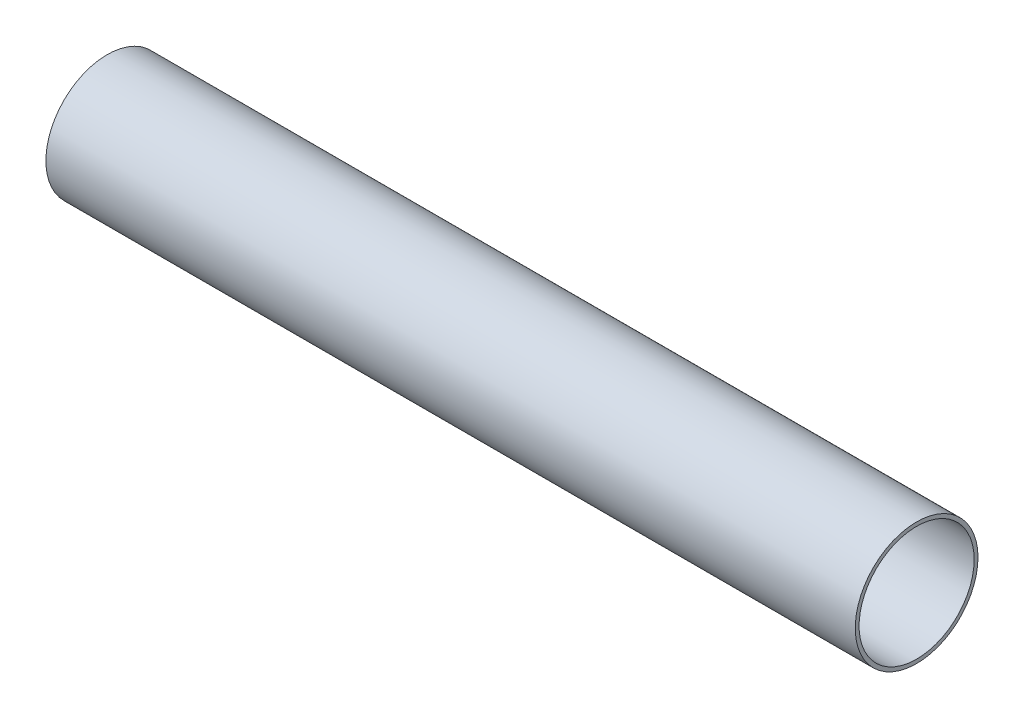
SolidWorks part; units mm, degrees
other "Exploded View1" [suppressed]
material "PC High Viscosity"
ref_plane "Front Plane" through (0, 0, 0) normal (0, 0, 1) x (1, 0, 0)
ref_plane "Top Plane" through (0, 0, 0) normal (0, 1, 0) x (1, 0, 0)
ref_plane "Right Plane" through (0, 0, 0) normal (1, 0, 0) x (0, 0, -1)
sketch "Sketch1" plane through (0, 0, 0) normal (1, 0, 0) x (0, 0, -1)
  circle A0 centre (0, 0) radius 25.4
  dimension "D1" = 50.8
extrude "Extrude-Thin1" add sketch "Sketch1" along normal mid plane 334.9625 thin thin type one direction reverse wall 1.5875
sketch "Sketch2" plane through (0, 0, 0) normal (0, 0, 1) x (1, 0, 0)
  line L0 (-167.4812, -25.4) -> (167.4812, -25.4) construction
  line L1 (112.2073, -25.4) -> (133.2072, -25.4)
  line L2 (112.2073, -25.4) -> (112.2073, 25.4)
  line L3 (112.2073, 25.4) -> (133.2072, 25.4)
  line L4 (133.2072, -25.4) -> (133.2072, 25.4)
  line L5 (167.4812, 25.4) -> (-167.4812, 25.4) construction
  line L6 (167.4812, -25.4) -> (167.4812, 25.4) construction
  line L7 (0, 0) -> (0, 11.1276) construction
  line L8 (-133.2072, -25.4) -> (-133.2072, 25.4)
  line L9 (-112.2073, 25.4) -> (-133.2072, 25.4)
  line L10 (-112.2073, -25.4) -> (-112.2073, 25.4)
  line L11 (-112.2073, -25.4) -> (-133.2072, -25.4)
  dimension "D1" = 34.274
  dimension "D2" = 21
equation "\"D2@Sketch2\"=21mm"
